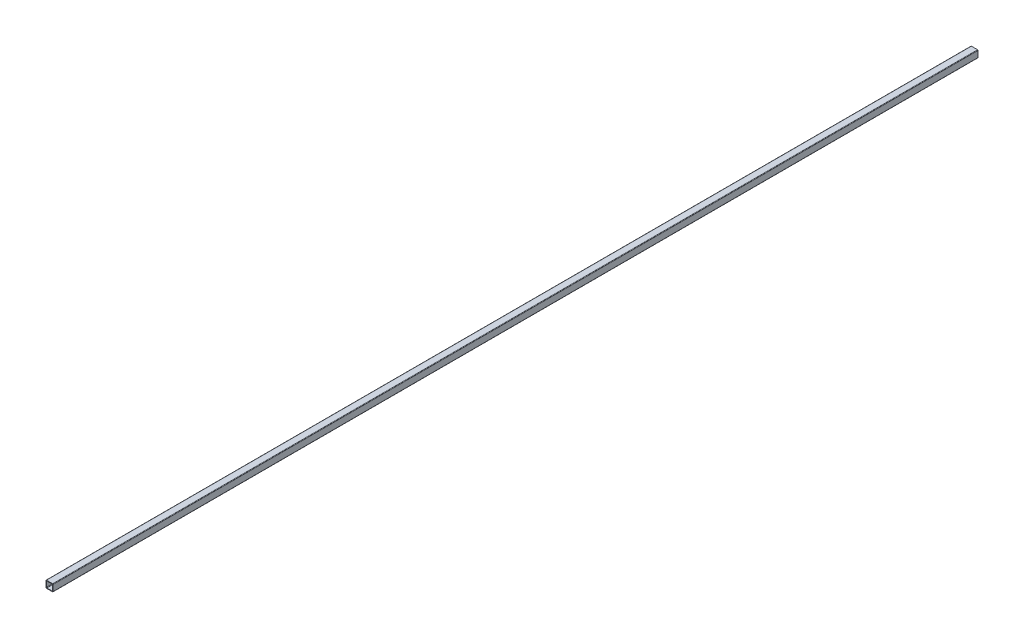
SolidWorks part; units mm, degrees
material "ASTM A500 Grade B"
ref_plane "Front Plane" through (0, 0, 0) normal (0, 0, 1) x (1, 0, 0)
ref_plane "Top Plane" through (0, 0, 0) normal (0, 1, 0) x (1, 0, 0)
ref_plane "Right Plane" through (0, 0, 0) normal (1, 0, 0) x (0, 0, -1)
sketch "Sketch1" plane through (0, 0, 0) normal (0, 0, 1) x (1, 0, 0)
  line L0 (5.3086, -2.7686) -> (32.7914, -2.7686)
  line L1 (2.54, 0) -> (35.56, 0)
  line L2 (0, -2.54) -> (0, -35.56)
  line L3 (2.54, -38.1) -> (35.56, -38.1)
  line L4 (38.1, -2.54) -> (38.1, -35.56)
  line L5 (35.3314, -5.3086) -> (35.3314, -32.7914)
  line L6 (5.3086, -35.3314) -> (32.7914, -35.3314)
  line L7 (2.7686, -5.3086) -> (2.7686, -32.7914)
  line L8 (0, 0) -> (0, -38.1) construction
  line L9 (0, -38.1) -> (38.1, -38.1) construction
  line L10 (38.1, 0) -> (38.1, -38.1) construction
  line L11 (2.7686, -2.7686) -> (2.7686, -35.3314) construction
  line L12 (2.7686, -35.3314) -> (35.3314, -35.3314) construction
  line L13 (35.3314, -2.7686) -> (35.3314, -35.3314) construction
  line L14 (2.7686, -2.7686) -> (35.3314, -2.7686) construction
  line L15 (0, 0) -> (38.1, 0) construction
  arc A0 (0, -35.56) -> (2.54, -38.1) centre (2.54, -35.56) ccw
  arc A1 (38.1, -35.56) -> (35.56, -38.1) centre (35.56, -35.56) cw
  arc A2 (2.7686, -32.7914) -> (5.3086, -35.3314) centre (5.3086, -32.7914) ccw
  arc A3 (32.7914, -35.3314) -> (35.3314, -32.7914) centre (32.7914, -32.7914) ccw
  arc A4 (35.3314, -5.3086) -> (32.7914, -2.7686) centre (32.7914, -5.3086) ccw
  arc A5 (38.1, -2.54) -> (35.56, 0) centre (35.56, -2.54) ccw
  arc A6 (0, -2.54) -> (2.54, 0) centre (2.54, -2.54) cw
  arc A7 (5.3086, -2.7686) -> (2.7686, -5.3086) centre (5.3086, -5.3086) ccw
  point P12 (0, -38.1)
  dimension "D4" = 2.54
  dimension "D3" = 2.7686
extrude "Boss-Extrude1" add sketch "Sketch1" along normal blind 5000
sketch "Sketch2" plane through (0, -38.1, 0) normal (0, -1, 0) x (-1, 0, 0)
  line L0 (-19.05, 0) -> (-19.05, -5000) construction
  line L1 (-2.54, 0) -> (-35.56, 0) construction
  line L2 (-2.54, -5000) -> (-35.56, -5000) construction
